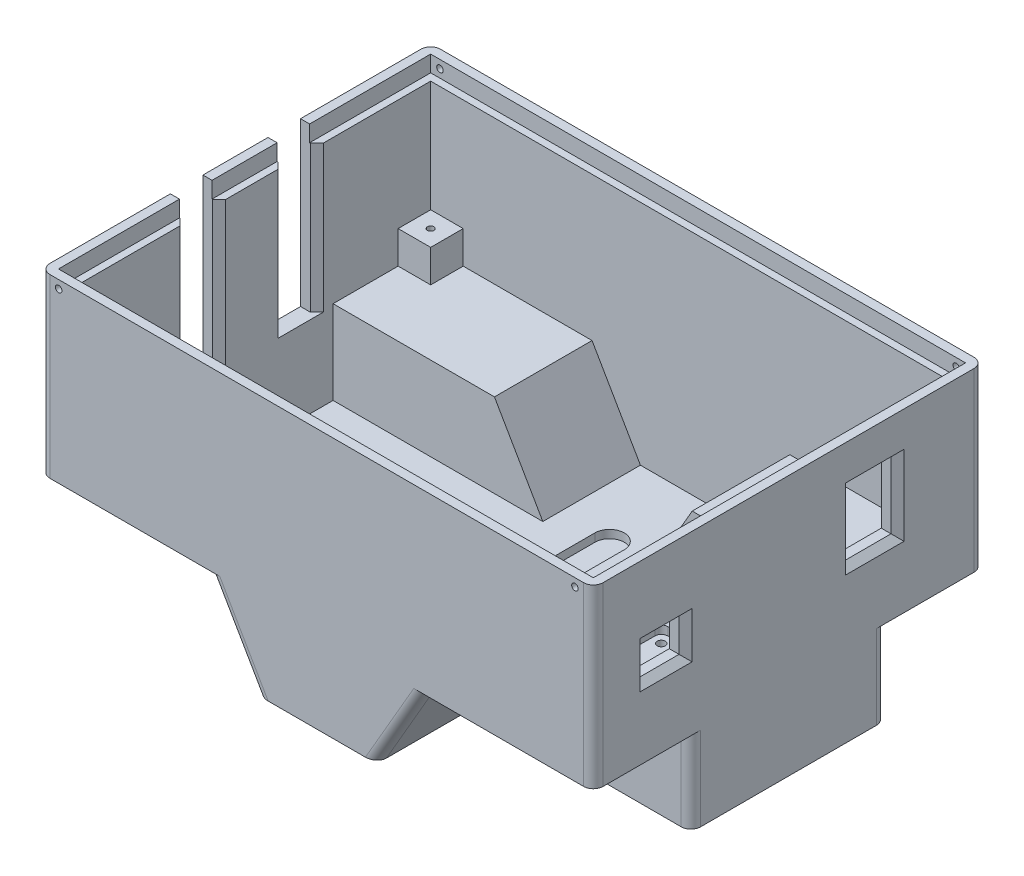
SolidWorks part; units mm, degrees
ref_plane "Plano frontal" through (0, 0, 0) normal (0, 0, 1) x (1, 0, 0)
ref_plane "Plano superior" through (0, 0, 0) normal (0, 1, 0) x (1, 0, 0)
ref_plane "Plano direito" through (0, 0, 0) normal (1, 0, 0) x (0, 0, -1)
sketch "Esboço7" plane through (0, 0, 0) normal (0, 1, 0) x (1, 0, 0)
  line L1 (85, -60) -> (-85, -60)
  line L2 (85, -60) -> (85, 60)
  line L3 (85, 60) -> (-85, 60)
  line L4 (-85, -60) -> (-85, 60)
  line L5 (85, -60) -> (-85, 60) construction
  line L6 (85, 60) -> (-85, -60) construction
  point P0 (0, 0)
  dimension "D1" = 120
  dimension "D2" = 170
extrude "Ressalto-extrusão4" add sketch "Esboço7" along normal blind 80 contours L4 L1 L2 L3 region at (0, 0, 0)
sketch "Esboço17" plane through (0, 0, 60) normal (0, 0, 1) x (1, 0, 0)
  line L0 (-85, 25.75) -> (-33.2819, 25.75)
  line L1 (-85, 80) -> (-85, 0) construction
  line L2 (-33.2819, 25.75) -> (-18.4152, 0)
  line L3 (85, 0) -> (-85, 0) construction
  line L4 (0, 0) -> (0, 80) construction
  line L5 (85, 80) -> (-85, 80) construction
  line L6 (-85, 25.75) -> (-85, 0)
  line L7 (-85, 0) -> (-18.4152, 0)
  line L8 (85, 0) -> (18.4152, 0)
  line L9 (85, 25.75) -> (85, 0)
  line L10 (85, 25.75) -> (33.2819, 25.75)
  line L11 (33.2819, 25.75) -> (18.4152, 0)
  line L12 (-53.5, 22.75) -> (-53.5, 25.75) construction
  line L13 (-18.4152, 0) -> (-21.4152, 0) construction
  circle A1 centre (-53.5, -11.25) radius 34
  circle A2 centre (-53.5, -11.25) radius 34 construction
  dimension "D3" = 3
  dimension "D1" = 60
  dimension "D4" = 3
  dimension "D2" = 0
extrude "Corte-extrusão9" cut sketch "Esboço17" against normal blind 30
mirror "Espelhar3" about plane through (0, 0, 0) normal (0, 0, 1) of "Corte-extrusão9"
shell "Casca1" thickness 5 removed face at (0, 80, 0)
sketch "Esboço9" plane through (0, 0, 0) normal (0, -1, 0) x (1, 0, 0)
  circle A16 centre (40.35, -13.25) radius 1.25 construction
  circle A17 centre (32.65, -13.25) radius 1.25 construction
  circle A18 centre (40.35, 13.25) radius 1.25 construction
  circle A19 centre (32.65, 13.25) radius 1.25 construction
  circle A20 centre (-30.15, 13.25) radius 1.25 construction
  circle A21 centre (-37.85, 13.25) radius 1.25 construction
  circle A22 centre (-30.15, -13.25) radius 1.25 construction
  circle A23 centre (-37.85, -13.25) radius 1.25 construction
  circle A24 centre (40.35, -13.25) radius 1.25
  circle A25 centre (32.65, -13.25) radius 1.25
  circle A26 centre (40.35, 13.25) radius 1.25
  circle A27 centre (32.65, 13.25) radius 1.25
  circle A28 centre (-30.15, 13.25) radius 1.25
  circle A29 centre (-37.85, 13.25) radius 1.25
  circle A30 centre (-30.15, -13.25) radius 1.25
  circle A31 centre (-37.85, -13.25) radius 1.25
extrude "Corte-extrusão4" cut sketch "Esboço9" against normal through all
sketch "Esboço10" plane through (0, 5, 0) normal (0, 1, 0) x (1, 0, 0)
  line L0 (0, 0) -> (36.5, 0) construction
  line L1 (40.35, -13.25) -> (32.65, 13.25) construction
  line L2 (41.35, 16.25) -> (31.65, 16.25)
  line L3 (43.35, 14.25) -> (43.35, -14.25)
  line L4 (41.35, -16.25) -> (31.65, -16.25)
  line L5 (29.65, 14.25) -> (29.65, -14.25)
  line L6 (43.35, 16.25) -> (29.65, -16.25) construction
  line L7 (43.35, -16.25) -> (29.65, 16.25) construction
  line L8 (0, 0) -> (0, -55) construction
  line L9 (15.5284, -55) -> (-15.5284, -55) construction
  line L10 (-30.15, 13.25) -> (-37.85, -13.25) construction
  line L12 (-38.85, 16.25) -> (-29.15, 16.25)
  line L13 (-40.85, 14.25) -> (-40.85, -14.25)
  line L14 (-38.85, -16.25) -> (-29.15, -16.25)
  line L15 (-27.15, 14.25) -> (-27.15, -14.25)
  line L16 (-40.85, 16.25) -> (-27.15, -16.25) construction
  line L17 (-40.85, -16.25) -> (-27.15, 16.25) construction
  arc A3 (-27.15, -14.25) -> (-29.15, -16.25) centre (-29.15, -14.25) cw
  arc A4 (-38.85, -16.25) -> (-40.85, -14.25) centre (-38.85, -14.25) cw
  arc A5 (-40.85, 14.25) -> (-38.85, 16.25) centre (-38.85, 14.25) cw
  arc A6 (-29.15, 16.25) -> (-27.15, 14.25) centre (-29.15, 14.25) cw
  arc A7 (43.35, -14.25) -> (41.35, -16.25) centre (41.35, -14.25) cw
  arc A8 (31.65, -16.25) -> (29.65, -14.25) centre (31.65, -14.25) cw
  arc A9 (29.65, 14.25) -> (31.65, 16.25) centre (31.65, 14.25) cw
  arc A10 (41.35, 16.25) -> (43.35, 14.25) centre (41.35, 14.25) cw
  point P4 (0, 0)
  point P13 (36.5, 0)
  point P25 (-34, 0)
  circle M37 centre (-30.15, -13.25) radius 1.25
  circle M38 centre (-37.85, -13.25) radius 1.25
  circle M39 centre (-30.15, 13.25) radius 1.25
  circle M40 centre (-37.85, 13.25) radius 1.25
  dimension "D3" = 2
  dimension "D1" = 3
  dimension "D2" = 3
extrude "Corte-extrusão5" cut sketch "Esboço10" against normal blind 2.5 contours L2 L5 L4 L3 | A6 L12 A5 L13 A4 L14 A3 L15 M37 M39 M40 M38 region at (36.5, 5, 0) region at (-34, 5, 0)
sketch "Esboço13" plane through (0, 80, 0) normal (0, 1, 0) x (1, 0, 0)
  circle A0 centre (0, 0) radius 4
  dimension "D1" = 8
extrude "Corte-extrusão7" cut sketch "Esboço13" against normal through all
sketch "Esboço14" plane through (0, 5, 0) normal (0, 1, 0) x (1, 0, 0)
  line L0 (0, -30) -> (0, 30) construction
  line L1 (-4.5, -30) -> (-4.5, 30)
  line L2 (4.5, -30) -> (4.5, 30)
  arc A0 (-4.5, -30) -> (4.5, -30) centre (0, -30) ccw
  arc A1 (4.5, 30) -> (-4.5, 30) centre (0, 30) ccw
  point P2 (0, 0)
  dimension "D1" = 60
  dimension "D2" = 9
extrude "Corte-extrusão8" cut sketch "Esboço14" against normal blind 2.5
sketch "Esboço22" plane through (80, 0, 0) normal (-1, 0, 0) x (0, 0, 1)
  line L0 (-33.5, 67.25) -> (-19.5, 67.25) construction
  line L4 (-33.5, 67.25) -> (-19.5, 67.25)
  line L5 (-33.5, 46.75) -> (-33.5, 67.25)
  line L6 (-19.5, 46.75) -> (-33.5, 46.75)
  line L7 (-19.5, 67.25) -> (-19.5, 46.75)
  line L8 (32.12, 57.45) -> (43.24, 57.45) construction
  line L9 (43.7, 56.89) -> (43.7, 47.24) construction
  line L10 (31.66, 47.24) -> (31.66, 56.89) construction
  line L11 (43.24, 47.24) -> (32.12, 47.24) construction
  line L12 (32.12, 57.45) -> (43.24, 57.45)
  line L13 (43.7, 56.89) -> (43.7, 47.24)
  line L14 (31.66, 47.24) -> (31.66, 56.89)
  line L15 (43.24, 47.24) -> (32.12, 47.24)
  line L16 (43.7, 56.89) -> (43.7, 57.45)
  line L17 (43.7, 57.45) -> (43.24, 57.45)
  line L19 (43.7, 57.45) -> (31.66, 57.45)
  line L20 (43.7, 57.45) -> (43.7, 47.24)
  line L21 (43.7, 47.24) -> (31.66, 47.24)
  line L22 (31.66, 57.45) -> (31.66, 47.24)
  line L23 (-33.5, 67.25) -> (-33.5, 46.75) construction
extrude "Corte-extrusão10" cut sketch "Esboço22" against normal through all contours L19 L22 L14 L21 L15 L13 L16 L17 L12 | L7 L4 L5 L6 region at (80, 57, -26.5) region at (80, 52.345, 37.68)
sketch "Esboço23" plane through (-80, 0, 0) normal (1, 0, 0) x (0, 0, -1)
  line L0 (0, 0) -> (0, 80) construction
  line L1 (-55, 80) -> (55, 80) construction
  line L2 (15, 0) -> (15, 80) construction
  line L3 (-15, 0) -> (-15, 80) construction
  line L5 (-20, 30) -> (-10, 30)
  line L6 (-20, 30) -> (-20, 80)
  line L7 (-20, 80) -> (-10, 80)
  line L8 (-10, 30) -> (-10, 80)
  line L9 (-20, 30) -> (-10, 80) construction
  line L10 (-20, 80) -> (-10, 30) construction
  line L11 (20, 30) -> (10, 30)
  line L12 (20, 30) -> (20, 80)
  line L13 (20, 80) -> (10, 80)
  line L14 (10, 30) -> (10, 80)
  line L15 (20, 30) -> (10, 80) construction
  line L16 (20, 80) -> (10, 30) construction
  point P9 (-15, 55)
  point P14 (15, 40)
  point P16 (15, 55)
  dimension "D1" = 15
  dimension "D3" = 10
  dimension "D4" = 50
  dimension "D2" = 15
extrude "Corte-extrusão11" cut sketch "Esboço23" against normal through all
chamfer "Chanfro1" distance 2 angle 45 4 edges at (-80, 55, 20) (-80, 55, -20) (-80, 55, -10) (-80, 55, 10)
ref_plane "Plano1" through (0, 70, 0) normal (0, 1, 0) x (1, 0, 0)
fillet "Filete2" radius 3 16 edges at (85, 12.875, 30) (85, 12.875, -30) (25.8485, 12.875, -30) (25.8485, 12.875, -60) (-25.8485, 12.875, -60) (-25.8485, 12.875, -30) (-85, 12.875, -30) (-85, 12.875, 30) (-25.8485, 12.875, 30) (25.8485, 12.875, 30) (25.8485, 12.875, 60) (-25.8485, 12.875, 60) (-85, 52.875, 60) (-85, 52.875, -60) (85, 52.875, -60) (85, 52.875, 60)
sketch "Esboço25" plane through (0, 80, 0) normal (0, 1, 0) x (1, 0, 0)
  line L0 (80, 55) -> (-80, 55) construction
  line L1 (82.2, -57.2) -> (-82.2, -57.2)
  line L2 (82.2, -57.2) -> (82.2, 57.2)
  line L3 (82.2, 57.2) -> (-82.2, 57.2)
  line L4 (-82.2, -57.2) -> (-82.2, 57.2)
  line L5 (82.2, -57.2) -> (-82.2, 57.2) construction
  line L6 (82.2, 57.2) -> (-82.2, -57.2) construction
  line L7 (-80, -55) -> (-80, -22) construction
  point P0 (0, 0)
  dimension "D1" = 2.2
  dimension "D2" = 2.2
extrude "Corte-extrusão12" cut sketch "Esboço25" against normal blind 5
sketch "Esboço26" plane through (0, 0, -60) normal (0, 0, -1) x (-1, 0, 0)
  circle A0 centre (-79.35, 77.5) radius 1 construction
  circle A1 centre (79.35, 77.5) radius 1 construction
  circle A2 centre (-79.35, 77.5) radius 1
  circle A3 centre (79.35, 77.5) radius 1
extrude "Corte-extrusão13" cut sketch "Esboço26" against normal through all
sketch "Esboço27" plane through (0, 30.75, 0) normal (0, 1, 0) x (1, 0, 0)
  line L1 (-70, 45) -> (-80, 45)
  line L2 (-70, 45) -> (-70, 55)
  line L3 (-70, 55) -> (-80, 55)
  line L4 (-80, 45) -> (-80, 55)
  line L5 (-70, 45) -> (-80, 55) construction
  line L6 (-70, 55) -> (-80, 45) construction
  line L7 (70, 45) -> (80, 45)
  line L8 (70, 45) -> (70, 55)
  line L9 (70, 55) -> (80, 55)
  line L10 (80, 45) -> (80, 55)
  line L11 (70, 45) -> (80, 55) construction
  line L12 (70, 55) -> (80, 45) construction
  line L13 (70, -45) -> (80, -45)
  line L14 (70, -45) -> (70, -55)
  line L15 (70, -55) -> (80, -55)
  line L16 (80, -45) -> (80, -55)
  line L17 (70, -45) -> (80, -55) construction
  line L18 (70, -55) -> (80, -45) construction
  line L19 (-70, -45) -> (-80, -45)
  line L20 (-70, -45) -> (-70, -55)
  line L21 (-70, -55) -> (-80, -55)
  line L22 (-80, -45) -> (-80, -55)
  line L23 (-70, -45) -> (-80, -55) construction
  line L24 (-70, -55) -> (-80, -45) construction
  circle A0 centre (-75, -50) radius 1 construction
  circle A1 centre (75, -50) radius 1 construction
  circle A2 centre (75, 50) radius 1 construction
  circle A3 centre (-75, 50) radius 1 construction
  circle A4 centre (-75, -50) radius 1 construction
  circle A5 centre (75, -50) radius 1 construction
  circle A6 centre (75, 50) radius 1 construction
  circle A7 centre (-75, 50) radius 1 construction
  circle A8 centre (75, -50) radius 1
  circle A9 centre (-75, -50) radius 1
  circle A10 centre (-75, 50) radius 1
  circle A11 centre (75, 50) radius 1
  dimension "D1" = 2
extrude "Ressalto-extrusão7" add sketch "Esboço27" along normal blind 10
chamfer "Chanfro2" distance 2 angle 45 8 edges at (85, 47.24, 37.68) (85, 52.345, 43.7) (85, 57.45, 37.68) (85, 52.345, 31.66) (85, 46.75, -26.5) (85, 57, -19.5) (85, 67.25, -26.5) (85, 57, -33.5)
ref_plane "Plano2" through (0, 30.75, 0) normal (0, 1, 0) x (1, 0, 0)
